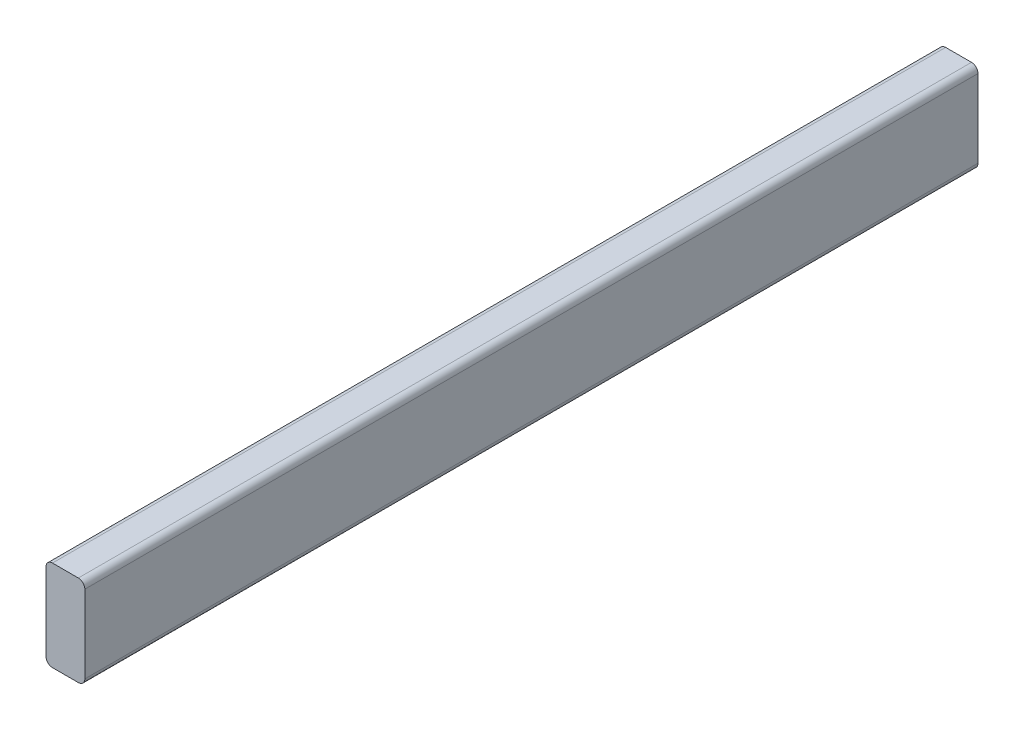
SolidWorks part; units mm, degrees
material "Oak"
ref_plane "Front Plane" through (0, 0, 0) normal (0, 0, 1) x (1, 0, 0)
ref_plane "Top Plane" through (0, 0, 0) normal (0, 1, 0) x (1, 0, 0)
ref_plane "Right Plane" through (0, 0, 0) normal (1, 0, 0) x (0, 0, -1)
sketch "Sketch2" plane through (0, 0, 0) normal (0, 0, 1) x (1, 0, 0)
  line L1 (-12.7, 44.45) -> (12.7, 44.45)
  line L2 (-19.05, 38.1) -> (-19.05, -38.1)
  line L3 (-12.7, -44.45) -> (12.7, -44.45)
  line L4 (19.05, 38.1) -> (19.05, -38.1)
  line L5 (-19.05, 44.45) -> (19.05, -44.45) construction
  line L6 (-19.05, -44.45) -> (19.05, 44.45) construction
  arc A0 (-19.05, -38.1) -> (-12.7, -44.45) centre (-12.7, -38.1) ccw
  arc A1 (12.7, -44.45) -> (19.05, -38.1) centre (12.7, -38.1) ccw
  arc A2 (12.7, 44.45) -> (19.05, 38.1) centre (12.7, 38.1) cw
  arc A3 (-12.7, 44.45) -> (-19.05, 38.1) centre (-12.7, 38.1) ccw
  point P0 (0, 0)
  dimension "D3" = 6.35
  dimension "D1" = 88.9
  dimension "D2" = 38.1
extrude "Boss-Extrude1" add sketch "Sketch2" along normal blind 876.3
